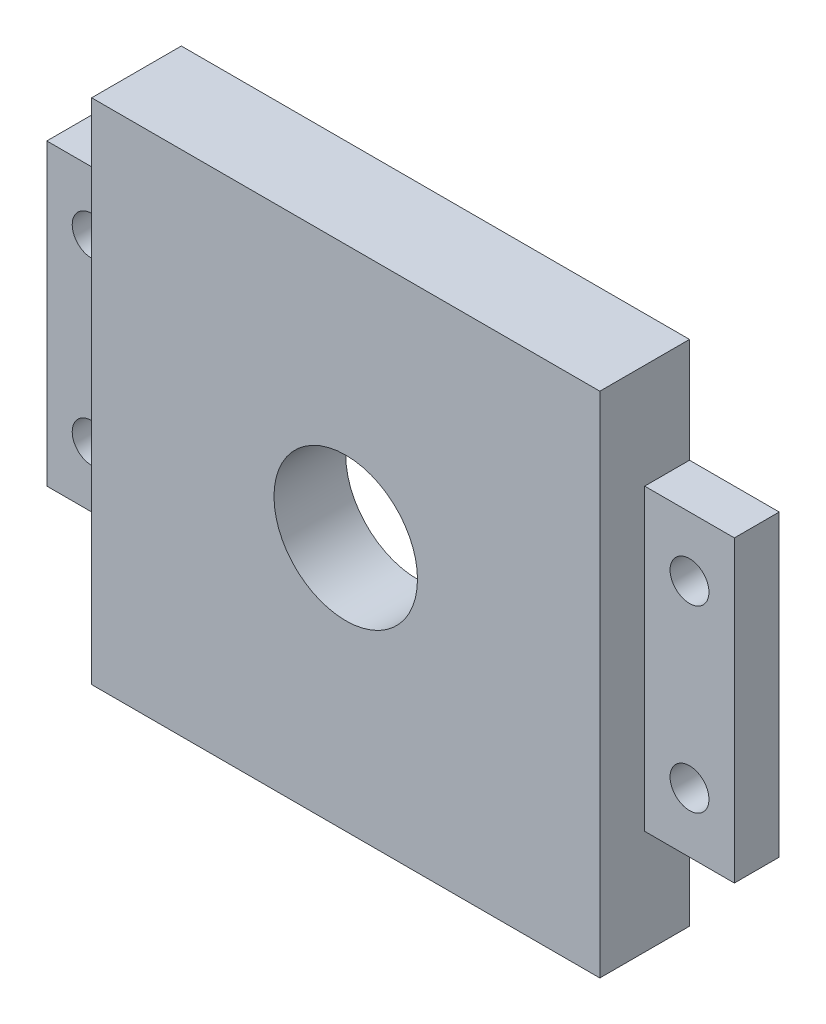
SolidWorks part; units mm, degrees
ref_plane "Płaszczyzna przednia" through (0, 0, 0) normal (0, 0, 1) x (1, 0, 0)
ref_plane "Płaszczyzna górna" through (0, 0, 0) normal (0, 1, 0) x (1, 0, 0)
ref_plane "Płaszczyzna prawa" through (0, 0, 0) normal (1, 0, 0) x (0, 0, -1)
sketch "Szkic1" plane through (0, 0, 0) normal (0, 0, 1) x (1, 0, 0)
  line L0 (42.5, 25) -> (42.5, 42.5)
  line L1 (-57.5, -25) -> (-42.5, -25)
  line L2 (-57.5, -25) -> (-57.5, 25)
  line L3 (-57.5, 25) -> (-42.5, 25)
  line L4 (57.5, -25) -> (57.5, 25)
  line L5 (-57.5, -25) -> (57.5, 25) construction
  line L6 (-57.5, 25) -> (57.5, -25) construction
  line L13 (42.5, -42.5) -> (-42.5, -42.5)
  line L14 (42.5, -42.5) -> (42.5, -25)
  line L15 (42.5, 42.5) -> (-42.5, 42.5)
  line L16 (-42.5, -42.5) -> (-42.5, -25)
  line L17 (42.5, -42.5) -> (-42.5, 42.5) construction
  line L18 (42.5, 42.5) -> (-42.5, -42.5) construction
  line L19 (42.5, -25) -> (57.5, -25)
  line L20 (-42.5, 25) -> (-42.5, 42.5)
  line L21 (42.5, 25) -> (57.5, 25)
  circle A0 centre (0, 0) radius 12
  point P0 (0, 0)
  dimension "D1" = 24
  dimension "D5" = 85
  dimension "D2" = 115
  dimension "D3" = 50
  dimension "D4" = 85
extrude "Dodanie-wyciągnięcie1" add sketch "Szkic1" along normal blind 15
sketch "Szkic6" plane through (0, 0, 0) normal (0, 0, -1) x (-1, 0, 0)
  line L0 (57.5, 25) -> (57.5, -25) construction
  line L1 (50, 15) -> (-50, 15) construction
  line L2 (50, 15) -> (50, -15) construction
  line L3 (50, -15) -> (-50, -15) construction
  line L4 (-50, 15) -> (-50, -15) construction
  line L5 (50, 15) -> (-50, -15) construction
  line L6 (50, -15) -> (-50, 15) construction
  line L7 (57.5, -25) -> (42.5, -25) construction
  circle A0 centre (-50, -15) radius 3.25
  circle A1 centre (-50, 15) radius 3.25
  circle A2 centre (50, 15) radius 3.25
  circle A3 centre (50, -15) radius 3.25
  point P0 (0, 0)
  dimension "D3" = 6.5
  dimension "D1" = 7.5
  dimension "D2" = 10
extrude "Wytnij-wyciągnięcie5" cut sketch "Szkic6" against normal through all
sketch "Szkic8" plane through (0, 0, 15) normal (0, 0, 1) x (1, 0, 0)
  line L0 (-57.5, -25) -> (-42.5, -25) construction
  line L1 (-57.5, 25) -> (-42.5, 25)
  line L2 (-57.5, 25) -> (-57.5, -25)
  line L3 (-57.5, -25) -> (-42.5, -25)
  line L4 (-42.5, 25) -> (-42.5, -25)
  line L5 (42.5, -25) -> (57.5, -25) construction
  line L6 (57.5, 25) -> (42.5, 25)
  line L7 (57.5, 25) -> (57.5, -25)
  line L8 (57.5, -25) -> (42.5, -25)
  line L9 (42.5, 25) -> (42.5, -25)
  dimension "D1" = 15
  dimension "D2" = 15
extrude "Wytnij-wyciągnięcie6" cut sketch "Szkic8" against normal blind 7.5
sketch "Szkic9" plane through (0, 0, 0) normal (0, 0, -1) x (-1, 0, 0)
  line L0 (0, 0) -> (0, 31.8198) construction
  line L6 (0, 31.8198) -> (-31.8198, 31.8198) construction
  line L7 (-31.8198, 31.8198) -> (0, 0) construction
  circle A0 centre (-31.8198, 31.8198) radius 2.5
  point P0 (0, 0)
  dimension "D2" = 5
  dimension "D1" = 45
extrude "Wytnij-wyciągnięcie7" cut sketch "Szkic9" against normal blind 10
cosmetic thread "Oznaczenie gwintu1" parameters "D1"=7.5, "D2"=6
ref_axis "Oś2" through (0, 0, 15) along (0, 0, -1)
pattern_circular "Szyk kołowy1" count 4 over 360 about axis through (0, 0, 15) along (0, 0, -1) of "Wytnij-wyciągnięcie7"
cosmetic thread "Oznaczenie gwintu2" parameters "D1"=7.5, "D2"=6
cosmetic thread "Oznaczenie gwintu3" parameters "D1"=7.5, "D2"=6
cosmetic thread "Oznaczenie gwintu4" parameters "D1"=7.5, "D2"=6
chamfer "Sfazowanie1" distance 0.5 angle 45 4 edges at (29.3198, 31.8198, 0) (31.8198, -29.3198, 0) (-29.3198, -31.8198, 0) (-31.8198, 29.3198, 0)
sketch "Szkic10" plane through (0, 0, 0) normal (0, 0, -1) x (-1, 0, 0)
  circle A0 centre (0, 0) radius 35
extrude "Wytnij-wyciągnięcie8" cut sketch "Szkic10" against normal blind 3
